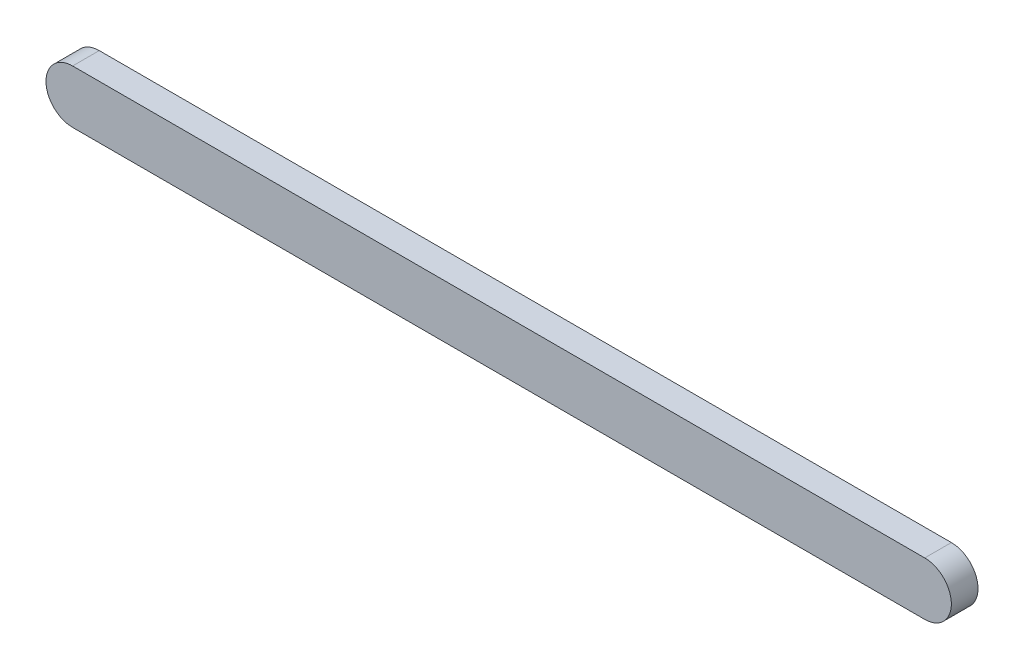
SolidWorks part; units mm, degrees
ref_plane "Front Plane" through (0, 0, 0) normal (0, 0, 1) x (1, 0, 0)
ref_plane "Top Plane" through (0, 0, 0) normal (0, 1, 0) x (1, 0, 0)
ref_plane "Right Plane" through (0, 0, 0) normal (1, 0, 0) x (0, 0, -1)
sketch "Sketch1" plane through (0, 0, 0) normal (0, 0, 1) x (1, 0, 0)
  line L0 (0, 0) -> (80, 0) construction
  line L1 (0, 2.5) -> (80, 2.5)
  line L2 (0, -2.5) -> (80, -2.5)
  arc A0 (0, 2.5) -> (0, -2.5) centre (0, 0) ccw
  arc A1 (80, -2.5) -> (80, 2.5) centre (80, 0) ccw
  point P3 (40, 0)
  dimension "D2" = 2.5
  dimension "D1" = 80
extrude "Boss-Extrude1" add sketch "Sketch1" along normal blind 2.5
sketch "Sketch2" plane through (0, 0, 2.5) normal (0, 0, 1) x (1, 0, 0)
  line L0 (0, -2.5) -> (80, -2.5) construction
  point P0 (0, 0)
  point P1 (80, 0)
ref_axis "Axis1" through (0, 0, 2.5) along (0, 0, 1)
ref_axis "Axis2" through (80, 0, 2.5) along (0, 0, 1)
